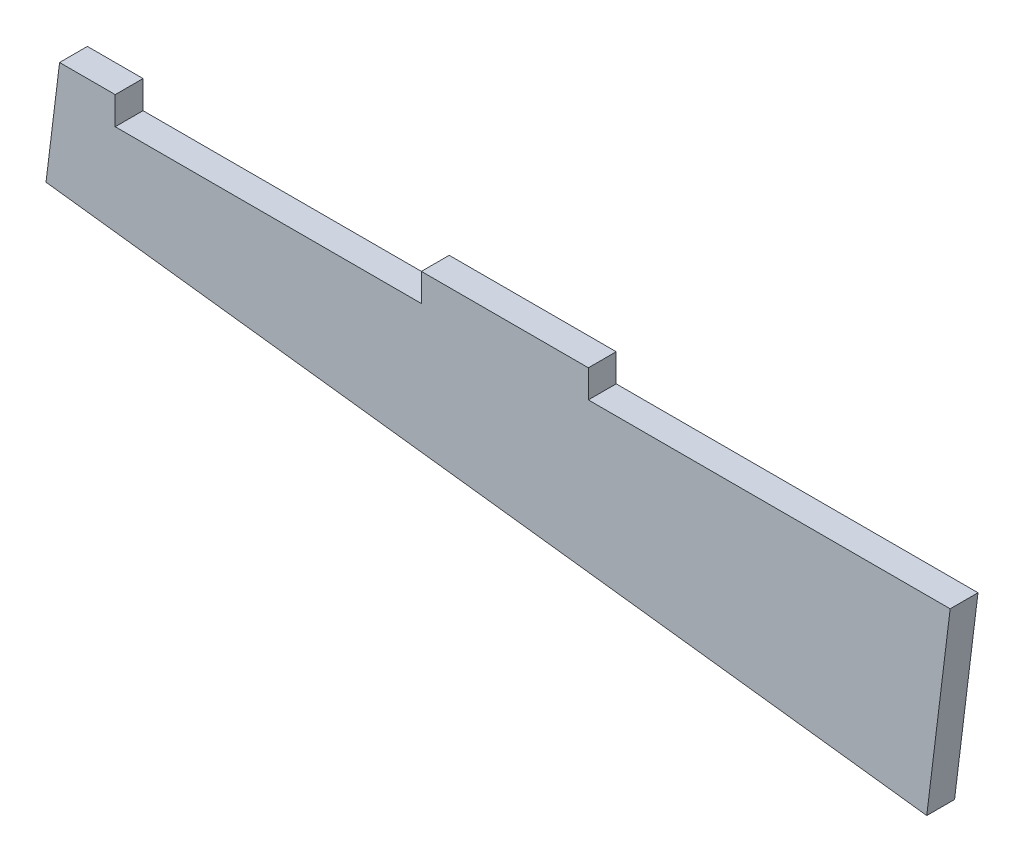
SolidWorks part; units mm, degrees
ref_plane "Front Plane" through (0, 0, 0) normal (0, 0, 1) x (1, 0, 0)
ref_plane "Top Plane" through (0, 0, 0) normal (0, 1, 0) x (1, 0, 0)
ref_plane "Right Plane" through (0, 0, 0) normal (1, 0, 0) x (0, 0, -1)
sketch "Sketch1" plane through (0, 0, 0) normal (0, 0, 1) x (1, 0, 0)
  line L0 (-195.3168, -62.6592) -> (-182.6168, -62.6592)
  line L4 (-182.6168, -62.6592) -> (-182.6168, -69.0092)
  line L5 (-182.6168, -69.0092) -> (-112.7668, -69.0092)
  line L6 (-112.7668, -69.0092) -> (-112.7668, -62.6592)
  line L7 (-112.7668, -62.6592) -> (-74.6668, -62.6592)
  line L8 (-74.6668, -62.6592) -> (-74.6668, -69.0092)
  line L9 (-74.6668, -69.0092) -> (7.8832, -69.0092)
  line L10 (7.8832, -69.0092) -> (2.5379, -112.5435)
  line L11 (2.5379, -112.5435) -> (-198.4122, -87.8699)
  line L12 (-198.4122, -87.8699) -> (-195.3168, -62.6592)
  line L13 (-374.6613, -18.9235) -> (-355.7533, -21.2451) construction
  dimension "D1" = 12.7
  dimension "D2" = 6.35
  dimension "D3" = 69.85
  dimension "D4" = 38.1
  dimension "D5" = 82.55
  dimension "D6" = 25.4
extrude "Boss-Extrude1" add sketch "Sketch1" against normal blind 6.35
